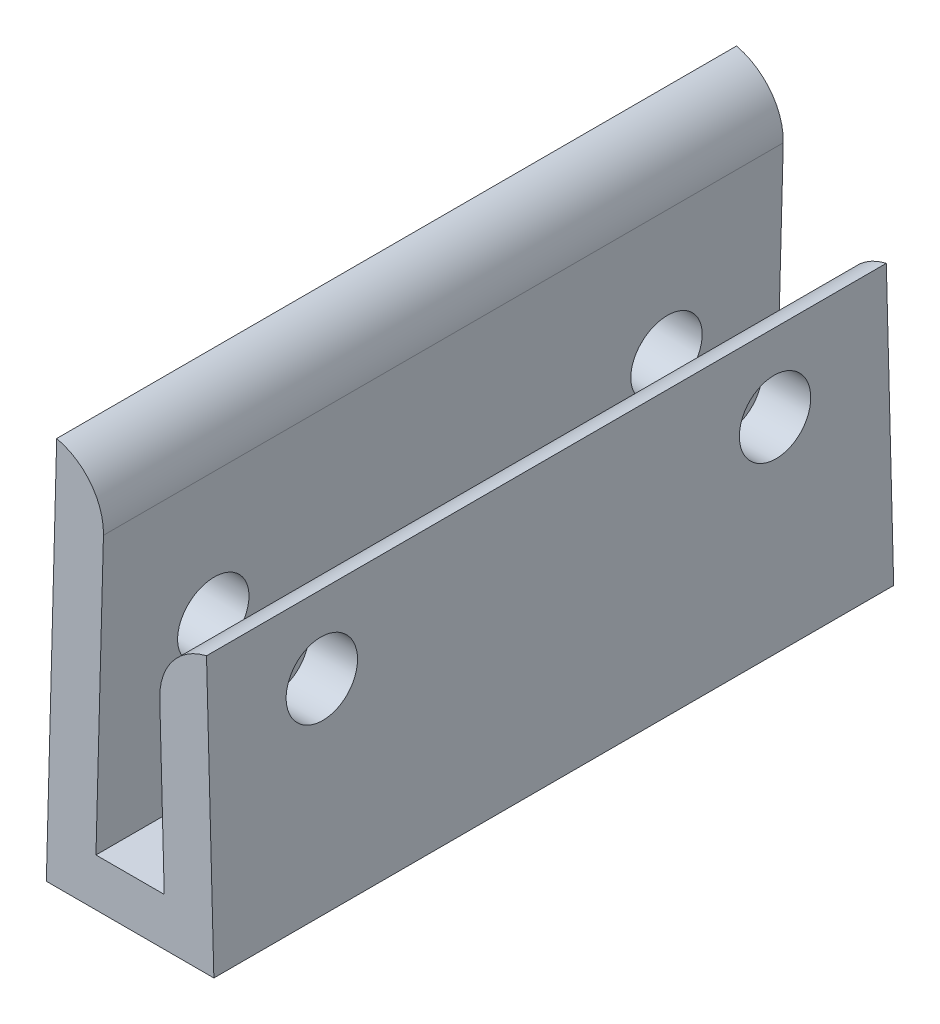
SolidWorks part; units mm, degrees
ref_plane "Front Plane" through (0, 0, 0) normal (0, 0, 1) x (1, 0, 0)
ref_plane "Top Plane" through (0, 0, 0) normal (0, 1, 0) x (1, 0, 0)
ref_plane "Right Plane" through (0, 0, 0) normal (1, 0, 0) x (0, 0, -1)
sketch "Sketch1" plane through (0, 0, 0) normal (0, 0, 1) x (1, 0, 0)
  line L0 (-3.5212, 0) -> (3.5212, 0)
  line L1 (3.5212, 0) -> (3.2124, 11.5758)
  line L2 (3.2124, 11.5758) -> (1.1811, 11.5216)
  line L3 (1.1811, 11.5216) -> (1.4351, 2)
  line L4 (1.4351, 2) -> (-1.4351, 2)
  line L5 (-1.4351, 2) -> (-1.1811, 11.5216)
  line L6 (-1.1811, 11.5216) -> (-3.2124, 11.5758)
  line L7 (-3.2124, 11.5758) -> (-3.5212, 0)
  line L8 (-3.2124, 11.5758) -> (-3.0854, 16.3366)
  line L9 (-3.0854, 16.3366) -> (-1.0541, 16.2824)
  line L10 (-1.0541, 16.2824) -> (-1.1811, 11.5216)
  point P11 (0, 0)
  point P13 (0, 2)
  dimension "D1" = 2.8702
  dimension "D2" = 2.3622
  dimension "D3" = 9.525
  dimension "D4" = 2.032
  dimension "D5" = 2
  dimension "D6" = 4.7625
extrude "Boss-Extrude1" add sketch "Sketch1" along normal blind 28.575 contours L6 L7 L0 L1 L2 L3 L4 L5 | L10 L9 L8 L6 region at (-3.2313, 5.7843, 0) region at (-2.1332, 13.9291, 0)
sketch "Sketch2" plane through (3.5187, 0.0939, 0) normal (0.9996, 0.0267, 0) x (0, 0, -1)
  line L0 (-23.8125, 8.311) -> (-4.7625, 8.311) construction
  line L1 (-28.575, 11.486) -> (0, 11.486) construction
  circle A0 centre (-23.8125, 8.311) radius 1.5
  circle A1 centre (-4.7625, 8.311) radius 1.5
  point P4 (-14.2875, 8.311)
  point P7 (-14.2875, 11.486)
  dimension "D1" = 3
  dimension "D3" = 19.05
  dimension "D2" = 6.35
extrude "Cut-Extrude1" cut sketch "Sketch2" against normal up to next
sketch "Sketch3" plane through (-3.5187, 0.0939, 0) normal (-0.9996, 0.0267, 0) x (0, 0, 1)
  line L0 (4.7625, 8.3063) -> (23.8125, 8.3063) construction
  line L2 (28.575, -0.0939) -> (0, -0.0939) construction
  circle A0 centre (4.7625, 8.3063) radius 1.5
  circle A1 centre (23.8125, 8.3063) radius 1.5
  point P4 (14.2875, 8.3063)
  point P8 (14.2875, -0.0939)
  dimension "D2" = 3
  dimension "D1" = 19.05
  dimension "D3" = 6.2687
extrude "Cut-Extrude2" cut sketch "Sketch3" against normal up to next
fillet "Fillet1" radius 2.54 2 edges at (1.1811, 11.5216, 14.2875) (-1.0541, 16.2824, 14.2875)
equation "\"bottomThickness\"= .220in"
equation "\"wallThickness\"= .118in"
equation "\"D2@Sketch1\"=\"wallThickness\"-.025in"
equation "\"D1@Sketch1\"=\"wallThickness\"-.005in"
